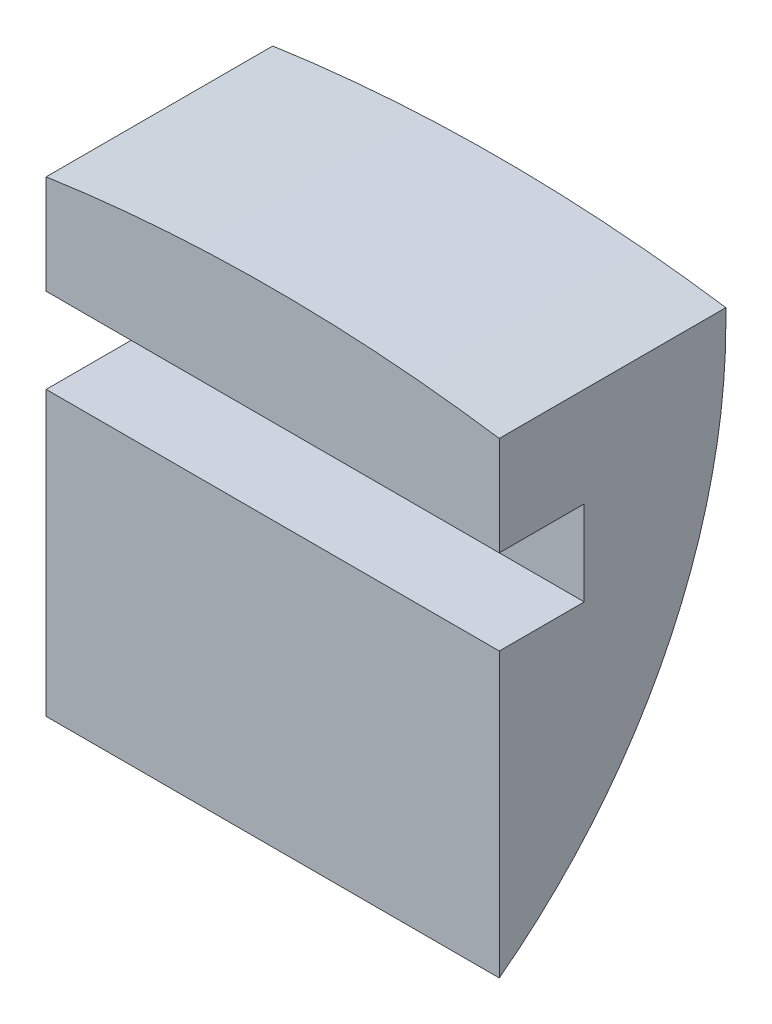
SolidWorks part; units mm, degrees
ref_plane "Alzado" through (0, 0, 0) normal (0, 0, 1) x (1, 0, 0)
ref_plane "Planta" through (0, 0, 0) normal (0, 1, 0) x (1, 0, 0)
ref_plane "Vista lateral" through (0, 0, 0) normal (1, 0, 0) x (0, 0, -1)
sketch "Croquis1" plane through (0, 0, 0) normal (0, 0, 1) x (1, 0, 0)
  line L1 (-4, 2.5) -> (4, 2.5)
  line L2 (-4, 2.5) -> (-4, -2.5)
  line L3 (-4, -2.5) -> (4, -2.5)
  line L4 (4, 2.5) -> (4, -2.5)
  line L5 (-4, 2.5) -> (4, -2.5) construction
  line L6 (-4, -2.5) -> (4, 2.5) construction
  point P0 (0, 0)
  dimension "D1" = 5
  dimension "D2" = 8
extrude "Saliente-Extruir1" add sketch "Croquis1" along normal blind 4
sketch "Croquis2" plane through (0, 0, 4) normal (0, 0, 1) x (1, 0, 0)
  line L0 (4, -2.5) -> (4, 2.5) construction
  line L1 (-4, 0.75) -> (4, 0.75)
  line L2 (-4, 0.75) -> (-4, -0.75)
  line L3 (-4, -0.75) -> (4, -0.75)
  line L4 (4, 0.75) -> (4, -0.75)
  line L5 (-4, 0.75) -> (4, -0.75) construction
  line L6 (-4, -0.75) -> (4, 0.75) construction
  point P0 (0, 0)
  dimension "D1" = 1.5
extrude "Cortar-Extruir1" cut sketch "Croquis2" against normal blind 1.5
sketch "Croquis3" plane through (0, 0, 4) normal (0, 0, 1) x (1, 0, 0)
  line L0 (4, -2.5) -> (4, -0.75) construction
  line L1 (-4, 2.5) -> (4, 2.5)
  line L3 (-4, -0.75) -> (4, -0.75)
  line L4 (-4, -0.75) -> (-4, -5.75)
  line L5 (-4, -5.75) -> (4, -5.75)
  line L6 (4, -0.75) -> (4, -5.75)
  arc A0 (-4, 2.5) -> (4, 2.5) centre (0, -24.7075) cw
  dimension "D1" = 27.5
  dimension "D2" = 5
extrude "Saliente-Extruir2" add sketch "Croquis3" against normal up to surface (4 mm away) up to face at (0, 0, 0)
fillet "Redondeo1" radius 10 1 edges at (0, -5.75, 0)
